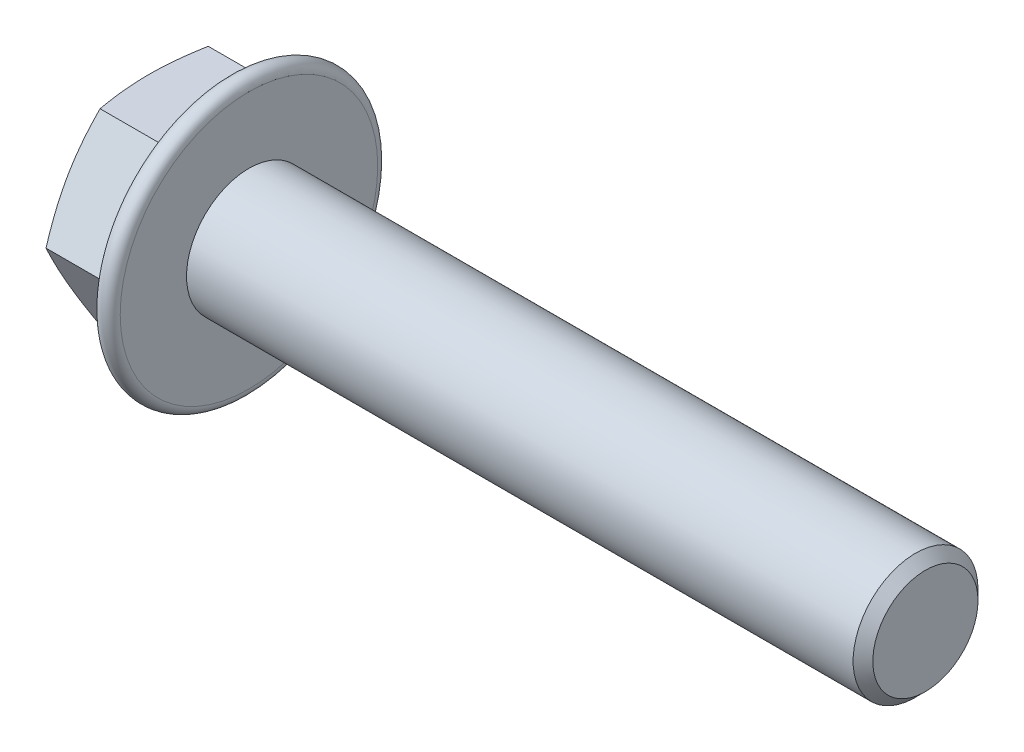
SolidWorks part; units mm, degrees
ref_plane "Front" through (0, 0, 0) normal (0, 0, 1) x (1, 0, 0)
ref_plane "Top" through (0, 0, 0) normal (0, 1, 0) x (1, 0, 0)
ref_plane "Right" through (0, 0, 0) normal (1, 0, 0) x (0, 0, -1)
other "Configuration Table"
sketch "Sketch1" plane through (0, 0, 0) normal (1, 0, 0) x (0, 0, -1)
  line L1 (10.3923, 0) -> (5.1962, 9)
  line L2 (5.1962, 9) -> (-5.1962, 9)
  line L3 (-5.1962, 9) -> (-10.3923, 0)
  line L4 (-10.3923, 0) -> (-5.1962, -9)
  line L5 (-5.1962, -9) -> (5.1962, -9)
  line L6 (5.1962, -9) -> (10.3923, 0)
  circle A0 centre (0, 0) radius 9 construction
extrude "BaseHead" add sketch "Sketch1" along normal blind 10.4
ref_plane "Plane1" through (45.4, 0, 0) normal (1, 0, 0) x (0, 0, -1)
sketch "Sketch2" plane through (10.4, 0, 0) normal (1, 0, 0) x (0, 0, -1)
  circle A0 centre (0, 0) radius 6
extrude "BaseBody" add sketch "Sketch2" along normal blind 65
cosmetic thread "ThreadCosmetic1" parameters "b"=30, "D2"=10.106
sketch "Sketch3" plane through (-0.4952, 0, 6.2687) normal (0, 1, 0) x (0, 0, -1)
  line L0 (16.661, -0.4952) -> (16.661, -1.7845)
  line L2 (16.661, -1.7845) -> (13.1187, -0.4952)
  line L4 (13.1187, -0.4952) -> (16.661, -0.4952)
  line L5 (6.2687, 4.1693) -> (6.2687, -11.9236) construction
  dimension "D1" = 20
revolve "HeadChamfer" cut sketch "Sketch3" angle 360 about L5
sketch "Sketch5" plane through (-0.1752, 0, 7.2752) normal (0, 1, 0) x (0, 0, -1)
  line L0 (7.2752, -10.5752) -> (7.2752, -7.1738) construction
  line L2 (7.2752, -10.5752) -> (19.6472, -10.5752)
  line L3 (19.9646, -8.7752) -> (7.2752, -4.1566)
  line L4 (7.2752, -4.1566) -> (7.2752, -10.5752)
  line L7 (7.2752, 4.4893) -> (7.2752, -11.6035) construction
  arc A0 (19.6472, -10.5752) -> (19.9646, -8.7752) centre (19.6472, -9.6472) ccw
  dimension "D3" = 20
  dimension "c" = 1.8
  dimension "dc" = 26.6
revolve "Flange" add sketch "Sketch5" angle 360 about L0
fillet "HeadFillet" [suppressed] radius 0.6
fillet "FlangeHexFillet" radius 0.7 6 edges
chamfer "Chamfer1" distance 0.947 angle 45 1 edges at (75.4, 0, -6)
sketch "Sketch6" plane through (0, 0, 0) normal (0, 0, 1) x (1, 0, 0)
  line L0 (73.506, 6.947) -> (74.453, 6.947)
  line L1 (74.453, 6.947) -> (74.453, 6)
  line L2 (74.453, 6) -> (73.9795, 5.1799)
  line L3 (73.9795, 5.1799) -> (73.506, 6)
  line L4 (73.506, 6) -> (73.506, 6.947)
  line L5 (74.453, 6) -> (10.4, 6) construction
  dimension "D1" = 0.947
revolve "Cut-Revolve10" [suppressed] cut sketch "Sketch6" angle 360
pattern_linear "LPattern10" [suppressed] count 26 of bodies 106
equation "\"D1@Chamfer1\" = (  \"d@Sketch2\" - \"D2@ThreadCosmetic1\" )  / 2"
equation "\"b@ThreadCosmetic1\" = \"l@BaseBody\" - \"lg@Plane1\""
equation "\"da@Sketch3\" = \"s@Sketch1\""
equation "\"D1@Sketch6\" =  ( \"d@Sketch2\" - \"D2@ThreadCosmetic1\" )  / 2"
equation "\"pitch@LPattern10\" = 1.2 * \"D1@Sketch6\""
equation "\"D1@LPattern10\" = \"b@ThreadCosmetic1\" / \"pitch@LPattern10\""
